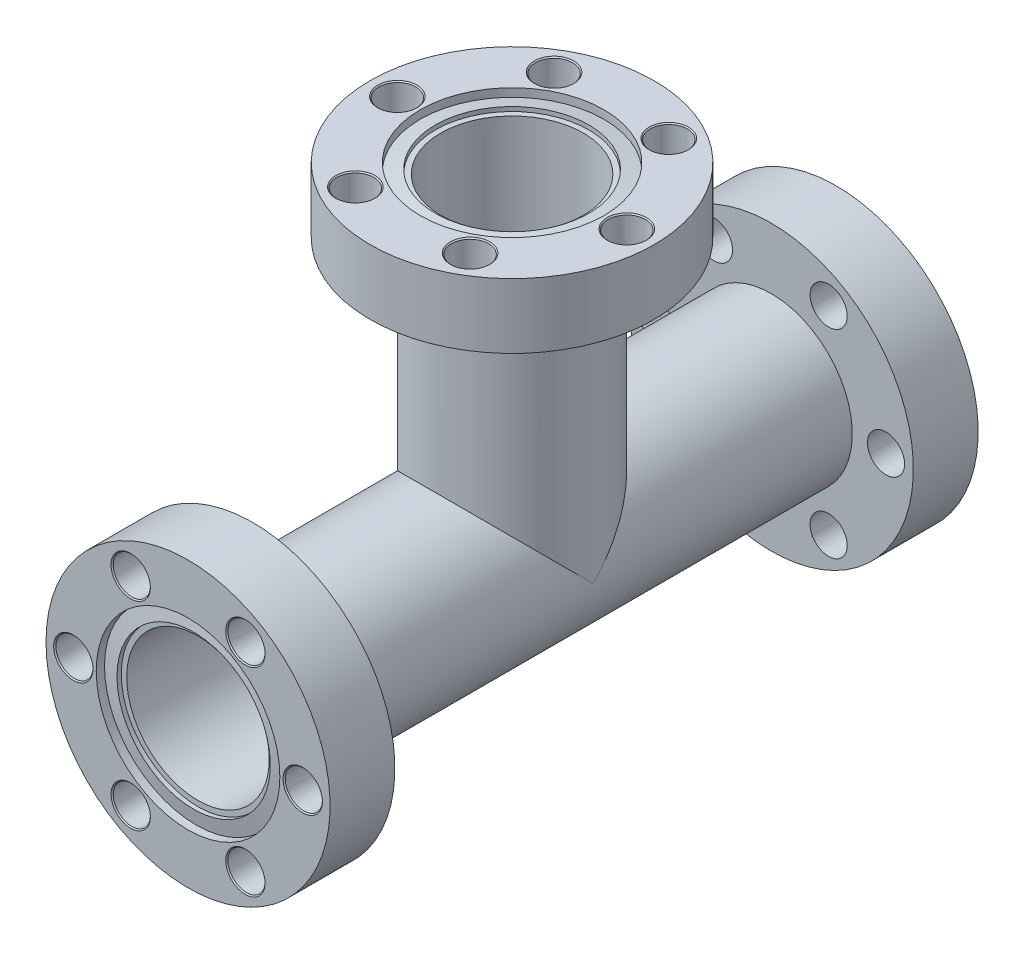
SolidWorks part; units mm, degrees
ref_plane "front" through (0, 0, 0) normal (0, 0, 1) x (1, 0, 0)
ref_plane "top" through (0, 0, 0) normal (0, 1, 0) x (1, 0, 0)
ref_plane "right" through (0, 0, 0) normal (1, 0, 0) x (0, 0, -1)
ref_axis "Axis1" through (0, 0, -80.9) along (0, 0, 1)
ref_axis "Axis2" through (-14.524, 0, 0) along (1, 0, 0)
sketch "Sketch3" plane through (0, 0, 0) normal (1, 0, 0) x (0, 0, -1)
  line L0 (30.48, 9.525) -> (30.48, 16.7005)
  line L1 (0, 9.525) -> (30.48, 9.525)
  line L2 (0, 9.525) -> (0, 0)
  line L3 (0, 0) -> (36.9316, 0)
  line L4 (30.48, 16.7005) -> (38.1, 16.7005)
  line L5 (38.1, 16.7005) -> (38.1, 10.795)
  line L6 (38.1, 10.795) -> (37.1261, 10.795)
  line L7 (37.1261, 10.795) -> (37.4396, 9.017)
  line L8 (37.4396, 9.017) -> (36.9316, 9.017)
  line L9 (36.9316, 9.017) -> (36.9316, 0)
  line L10 (36.9316, 0) -> (53.2968, 0) construction
  dimension "D1" = 19.05
  dimension "D2" = 33.401
  dimension "D3" = 7.62
  dimension "D4" = 0.6604
  dimension "D5" = 1.1684
  dimension "D6" = 21.59
  dimension "D7" = 18.034
  dimension "D8" = 10
  dimension "D9" = 38.1
revolve "Revolve1" add sketch "Sketch3" angle 360 about axis through (0, 0, -80.9) along (0, 0, 1)
hole_wizard "11/64 (0.17188) Diameter Hole1" positions "Sketch5" profile "Sketch4" hole size "11/64" standard "Ansi Inch"
sketch "Sketch5" plane through (0, 0, -38.1) normal (0, 0, -1) x (-1, 0, 0)
  point P0 (13.4874, 0)
  dimension "D1" = 13.4874
sketch "Sketch4" plane through (-13.4874, 0, -38.1) normal (1, 0, 0) x (0, 1, 0)
  line L0 (0, 0) -> (0, 8.9316)
  line L1 (0, 8.9316) -> (2.1829, 7.62)
  line L2 (2.1829, 7.62) -> (2.1829, 0.1285)
  line L3 (2.1829, 0.1285) -> (2.3114, 0)
  line L5 (2.3114, 0) -> (0, 0)
  line L6 (-2.1829, 0.1285) -> (-2.3114, 0) construction
  line L10 (0, 8.9316) -> (-2.1829, 7.62) construction
  line L11 (0, -6.35) -> (0, 107.95) construction
  dimension "Hole Dia." = 4.3658
  dimension "Hole Depth" = 7.62
  dimension "Near C'Sink Dia." = 4.6228
  dimension "Near C'Sink Angle" = 90
  dimension "Drill Angle" = 118
pattern_circular "CirPattern1" count 6 over 360 about axis through (0, 0, -80.9) along (0, 0, 1) of "11/64 (0.17188) Diameter Hole1"
pattern_circular "CirPattern5" count 3 every 90 about axis through (-14.524, 0, 0) along (1, 0, 0) of "11/64 (0.17188) Diameter Hole1", "Revolve1", "CirPattern1"
sketch "Sketch6" plane through (0, 0, 0) normal (0, 0, 1) x (1, 0, 0)
  circle A0 centre (0, 0) radius 8.382
  dimension "D1" = 16.764
extrude "Cut-Extrude1" cut sketch "Sketch6" against normal mid plane 101.6
sketch "Sketch7" plane through (0, 0, 0) normal (0, 1, 0) x (1, 0, 0)
  circle A0 centre (0, 0) radius 8.382
  dimension "D1" = 16.764
extrude "Cut-Extrude2" cut sketch "Sketch7" along normal blind 50.8
